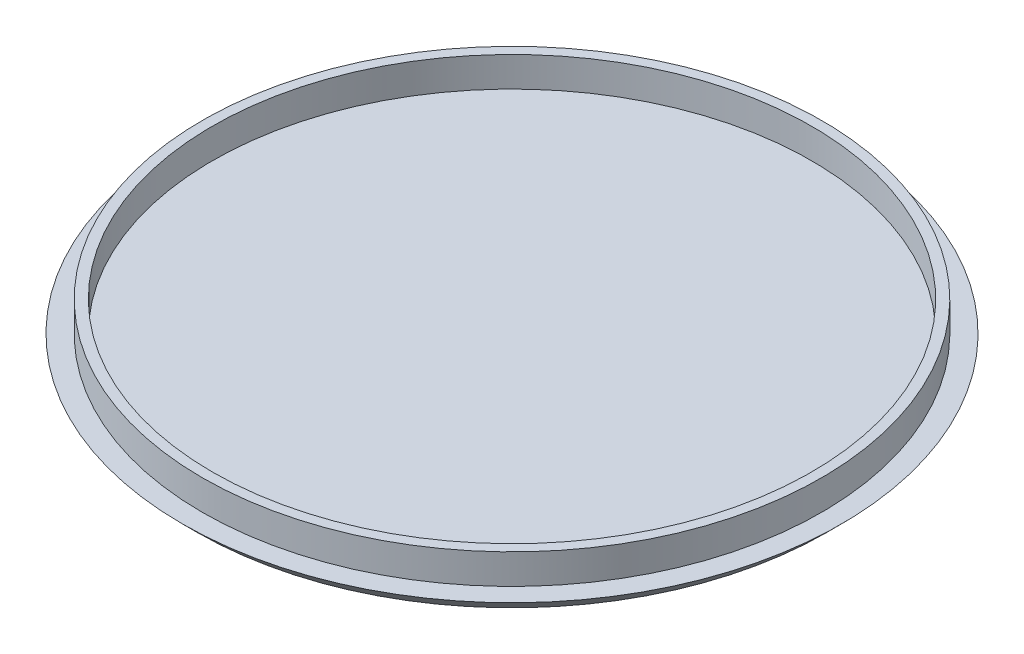
SolidWorks part; units mm, degrees
ref_plane "Front Plane" through (0, 0, 0) normal (0, 0, 1) x (1, 0, 0)
ref_plane "Top Plane" through (0, 0, 0) normal (0, 1, 0) x (1, 0, 0)
ref_plane "Right Plane" through (0, 0, 0) normal (1, 0, 0) x (0, 0, -1)
sketch "Sketch2" plane through (0, 0, 0) normal (0, 1, 0) x (1, 0, 0)
  circle A0 centre (0, 0) radius 16.5
  dimension "D1" = 33
extrude "Boss-Extrude1" add sketch "Sketch2" along normal blind 0.75
sketch "Sketch3" plane through (0, 0.75, 0) normal (0, 1, 0) x (1, 0, 0)
  circle A0 centre (0, 0) radius 15.5
  circle A1 centre (0, 0) radius 15
  dimension "D1" = 31
  dimension "D2" = 30
extrude "Boss-Extrude2" add sketch "Sketch3" along normal blind 1.5
chamfer "Chamfer1" distance 0.75 angle 45 1 edges at (0, 0, 16.5)
